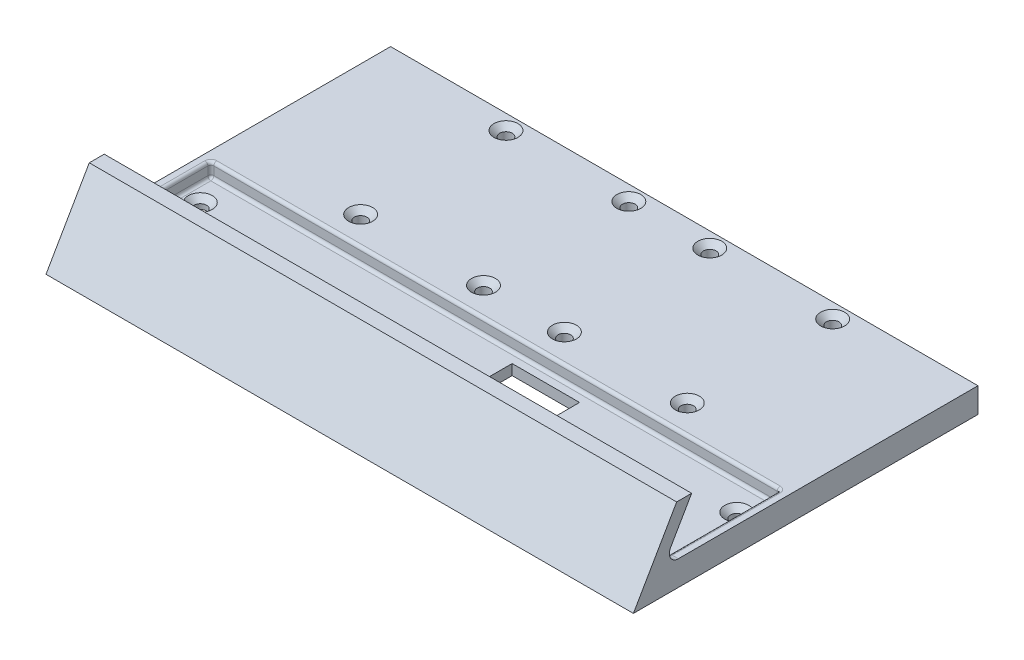
SolidWorks part; units mm, degrees
ref_plane "Alzado" through (0, 0, 0) normal (0, 0, 1) x (1, 0, 0)
ref_plane "Planta" through (0, 0, 0) normal (0, 1, 0) x (1, 0, 0)
ref_plane "Vista lateral" through (0, 0, 0) normal (1, 0, 0) x (0, 0, -1)
sketch "Sketch1" plane through (0, 0, 0) normal (1, 0, 0) x (0, 0, -1)
  line L0 (-13.9334, 0) -> (0.5004, 25)
  line L1 (-88.9489, -50.86) -> (38.0613, -50.86) construction
  line L2 (0.5004, 25) -> (5.5004, 25)
  line L3 (5.5004, 25) -> (-8.9334, 0)
  line L4 (-8.9334, 0) -> (-13.9334, 0)
  dimension "D1" = 120
  dimension "D2" = 25
  dimension "D3" = 5
  dimension "D4" = 5
extrude "Boss-Extrude1" add sketch "Sketch1" along normal blind 196
sketch "Sketch2" plane through (0, 0, 0) normal (1, 0, 0) x (0, 0, -1)
  line L0 (42.0107, 0) -> (42.0107, 4.8111)
  line L1 (101.0511, 0) -> (101.0511, -50.86) construction
  line L6 (-11.9127, 3.5) -> (-13.9334, 0)
  line L8 (-11.9127, 3.5) -> (38.0613, 3.5)
  line L9 (-13.9334, 0) -> (38.0613, 0)
  line L10 (42.0107, 4.8111) -> (101.0511, 4.8111)
  line L16 (101.0511, 4.8111) -> (101.0511, 8.3111)
  line L17 (101.0511, 8.3111) -> (38.0613, 8.3111)
  line L18 (38.0613, 8.3111) -> (38.0613, 3.5)
  line L19 (38.0613, 0) -> (42.0107, 0)
  dimension "D1" = 3.5
  dimension "D2" = 3.5
extrude "Boss-Extrude2" add sketch "Sketch2" along normal blind 196
sketch "Sketch3" plane through (0, 0, 0) normal (0, -1, 0) x (1, 0, 0)
  circle A0 centre (187.5, -29.0613) radius 1.585
  circle A1 centre (8.5, -29.0613) radius 1.585
  circle A2 centre (43.5, -47.5511) radius 1.585
  circle A3 centre (84.5, -47.5511) radius 1.585
  circle A4 centre (111.5, -47.5511) radius 1.585
  circle A5 centre (152.5, -47.5511) radius 1.585
  circle A6 centre (152.5, -96.0511) radius 1.585
  circle A7 centre (111.5, -96.0511) radius 1.585
  circle A8 centre (84.5, -96.0511) radius 1.585
  circle A9 centre (43.5, -96.0511) radius 1.585
extrude "Cut-Extrude2" cut sketch "Sketch3" against normal through all and the other way through all
hole_wizard "Avellanado para tornillo con cabeza avellanada en cruz de M3.52" positions "3DSketch2" profile "Sketch6" countersink size "M3.5" standard "AS"
sketch3d "3DSketch2"
  line L0 (152.5, 8.3111, -47.5511) -> (152.5, 4.8111, -47.5511) construction
  line L1 (187.5, 3.5, -29.0613) -> (187.5, 0, -29.0613) construction
  line L2 (111.5, 8.3111, -47.5511) -> (111.5, 4.8111, -47.5511) construction
  line L3 (111.5, 8.3111, -96.0511) -> (111.5, 4.8111, -96.0511) construction
  line L4 (152.5, 8.3111, -96.0511) -> (152.5, 4.8111, -96.0511) construction
  line L5 (84.5, 8.3111, -96.0511) -> (84.5, 4.8111, -96.0511) construction
  line L6 (84.5, 8.3111, -47.5511) -> (84.5, 4.8111, -47.5511) construction
  line L7 (43.5, 8.3111, -47.5511) -> (43.5, 4.8111, -47.5511) construction
  line L8 (43.5, 8.3111, -96.0511) -> (43.5, 4.8111, -96.0511) construction
  line L9 (8.5, 3.5, -29.0613) -> (8.5, 0, -29.0613) construction
  point P0 (152.5, 8.3111, -47.5511)
  point P4 (187.5, 3.5, -29.0613)
  point P8 (111.5, 8.3111, -47.5511)
  point P12 (111.5, 8.3111, -96.0511)
  point P16 (152.5, 8.3111, -96.0511)
  point P20 (84.5, 8.3111, -96.0511)
  point P24 (84.5, 8.3111, -47.5511)
  point P28 (43.5, 8.3111, -47.5511)
  point P32 (43.5, 8.3111, -96.0511)
  point P36 (8.5, 3.5, -29.0613)
sketch "Sketch6" plane through (152.5, 8.3111, -47.5511) normal (1, 0, 0) x (0, 0, 1)
  line L0 (0, 0) -> (0, 11.2618)
  line L1 (0, 11.2618) -> (2.1, 10)
  line L2 (2.1, 10) -> (2.1, 1.8348)
  line L3 (2.1, 1.8348) -> (4, 0)
  line L5 (4, 0) -> (0, 0)
  line L6 (-2.1, 1.8348) -> (-4, 0) construction
  line L10 (0, 11.2618) -> (-2.1, 10) construction
  line L11 (0, -6.35) -> (0, 107.95) construction
  dimension "Diámetro de taladro" = 4.2
  dimension "Profundidad de taladro" = 10
  dimension "Ángulo de avellanado cercano" = 8
  dimension "Ángulo de avellanado lejano" = 92
  dimension "Ángulo de perforador" = 118
sketch "Sketch10" plane through (0, 0, 0) normal (0, -1, 0) x (-1, 0, 0)
  line L1 (-67.6351, -5.9334) -> (-90.1351, -5.9334)
  line L2 (-67.6351, -5.9334) -> (-67.6351, 2.0666)
  line L3 (-67.6351, 2.0666) -> (-90.1351, 2.0666)
  line L4 (-90.1351, -5.9334) -> (-90.1351, 2.0666)
  line L5 (-67.6351, -5.9334) -> (-90.1351, 2.0666) construction
  line L6 (-67.6351, 2.0666) -> (-90.1351, -5.9334) construction
  line L7 (-107.0575, 22.5466) -> (-129.5575, 22.5466)
  line L8 (-107.0575, 22.5466) -> (-107.0575, 34.5466)
  line L9 (-107.0575, 34.5466) -> (-129.5575, 34.5466)
  line L10 (-129.5575, 22.5466) -> (-129.5575, 34.5466)
  line L11 (-107.0575, 22.5466) -> (-129.5575, 34.5466) construction
  line L12 (-107.0575, 34.5466) -> (-129.5575, 22.5466) construction
  point P4 (-78.8851, -1.9334)
  point P9 (-118.3075, 28.5466)
extrude "Cut-Extrude4" cut sketch "Sketch10" against normal blind 4
fillet "Fillet4" radius 5 1 edges at (78.8851, 3.5, -2.0666)
sketch "Sketch11" plane through (0, 0, 0) normal (1, 0, 0) x (0, 0, -1)
  line L1 (40.0605, 8.3111) -> (-8.2744, 8.3111)
  line L2 (40.0605, 8.3111) -> (40.0605, 1.9288)
  line L3 (40.0605, 1.9288) -> (-8.2744, 1.9288)
  line L4 (-8.2744, 8.3111) -> (-8.2744, 1.9288)
  line L5 (40.0605, 8.3111) -> (-8.2744, 1.9288) construction
  line L6 (40.0605, 1.9288) -> (-8.2744, 8.3111) construction
  point P4 (15.893, 5.12)
extrude "Boss-Extrude4" add sketch "Sketch11" along normal blind 3
ref_plane "Plane2" through (98, 0, 0) normal (-1, 0, 0) x (0, 0, 1)
mirror "Mirror1" about plane through (98, 0, 0) normal (-1, 0, 0) of "Boss-Extrude4"
fillet "Fillet5" radius 1 8 edges at (3, 5.9056, -38.0613) (193, 5.9056, -38.0613) (98, 3.5, -38.0613) (193, 3.5, -15.5743) (3, 3.5, -15.5743) (3, 5.9056, 5.5238) (98, 3.5, 6.9127) (193, 5.9056, 5.5238)
fillet "Fillet6" radius 3 2 edges at (2, 8.3111, 4.135) (194, 8.3111, 4.135)
fillet "Fillet7" radius 1 9 edges at (192.6599, 11.6512, 1.9195) (193, 8.8812, 0.6981) (193, 8.3111, -19.0612) (192.7071, 8.3111, -37.7684) (3.3401, 11.6512, 1.9195) (3, 8.8812, 0.6981) (3, 8.3111, -19.0612) (3.2929, 8.3111, -37.7684) (98, 8.3111, -38.0613)
sketch "Sketch12" plane through (0, 4.8111, 0) normal (0, -1, 0) x (1, 0, 0)
  line L1 (0, -101.0511) -> (196, -101.0511)
  line L2 (0, -101.0511) -> (0, -42.0107)
  line L3 (0, -42.0107) -> (196, -42.0107)
  line L4 (196, -101.0511) -> (196, -42.0107)
  line L5 (0, -101.0511) -> (196, -42.0107) construction
  line L6 (0, -42.0107) -> (196, -101.0511) construction
  point P4 (98, -71.5309)
extrude "Boss-Extrude5" add sketch "Sketch12" along normal up to vertex (4.8111 mm away) up to point (196, 0, -42.0107)
sketch "Sketch9" plane through (0, 8.3111, 0) normal (0, 1, 0) x (1, 0, 0)
  circle A0 centre (43.5, 47.5511) radius 2.1
  circle A1 centre (84.5, 47.5511) radius 2.1
  circle A2 centre (152.5, 47.5511) radius 2.1
  circle A3 centre (152.5, 96.0511) radius 2.1
  circle A4 centre (111.5, 96.0511) radius 2.1
  circle A5 centre (111.5, 47.5511) radius 2.1
  circle A7 centre (84.5, 96.0511) radius 2.1
  circle A8 centre (43.5, 96.0511) radius 2.1
extrude "Cut-Extrude5" cut sketch "Sketch9" against normal up to next
